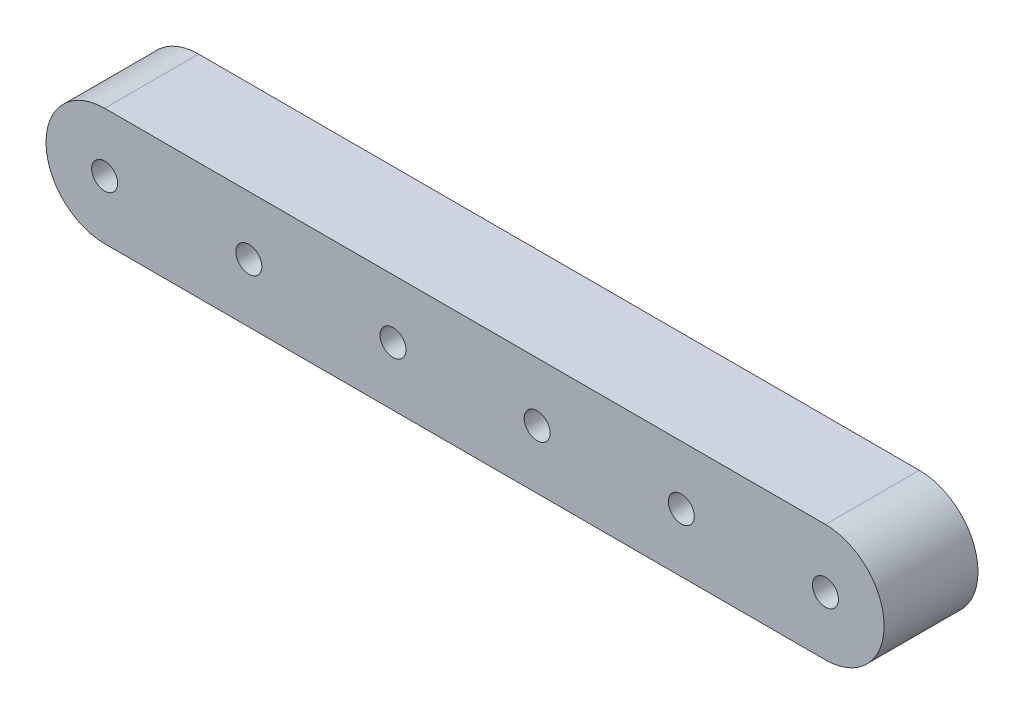
SolidWorks part; units mm, degrees
ref_plane "Front Plane" through (0, 0, 0) normal (0, 0, 1) x (1, 0, 0)
ref_plane "Top Plane" through (0, 0, 0) normal (0, 1, 0) x (1, 0, 0)
ref_plane "Right Plane" through (0, 0, 0) normal (1, 0, 0) x (0, 0, -1)
sketch "Sketch1" plane through (0, 0, 0) normal (0, 0, 1) x (1, 0, 0)
  line L0 (-33.3096, 0) -> (9.6904, 0) construction
  line L1 (-33.3096, 3.5) -> (9.6904, 3.5)
  line L2 (-33.3096, -3.5) -> (9.6904, -3.5)
  arc A0 (-33.3096, 3.5) -> (-33.3096, -3.5) centre (-33.3096, 0) ccw
  arc A1 (9.6904, -3.5) -> (9.6904, 3.5) centre (9.6904, 0) ccw
  point P3 (-11.8096, 0)
  point P8 (-36.8096, 0)
  point P9 (13.1904, 0)
  dimension "D1" = 50
  dimension "D2" = 7
extrude "Boss-Extrude1" add sketch "Sketch1" along normal blind 2.8 and the other way blind 2.8
scale "Echelle1" scale about centroid uniform scaling yes scale factor 2
sketch "Sketch2" plane through (0, 0, -5.6) normal (0, 0, 1) x (1, 0, 0)
  circle A7 centre (-54.8096, 0) radius 1.55
  circle A28 centre (-37.6096, 0) radius 1.55
  circle A29 centre (-20.4096, 0) radius 1.55
  circle A30 centre (-3.2096, 0) radius 1.55
  circle A31 centre (13.9904, 0) radius 1.55
  circle A32 centre (31.1904, 0) radius 1.55
  dimension "D1" = 3.1
  dimension "D2" = 6
extrude "Cut-Extrude6" cut sketch "Sketch2" along normal up to surface (11.2 mm away) up to face at (-11.8096, 0, 5.6)
equation "\"ScrewSize\"= 2.9mm"
